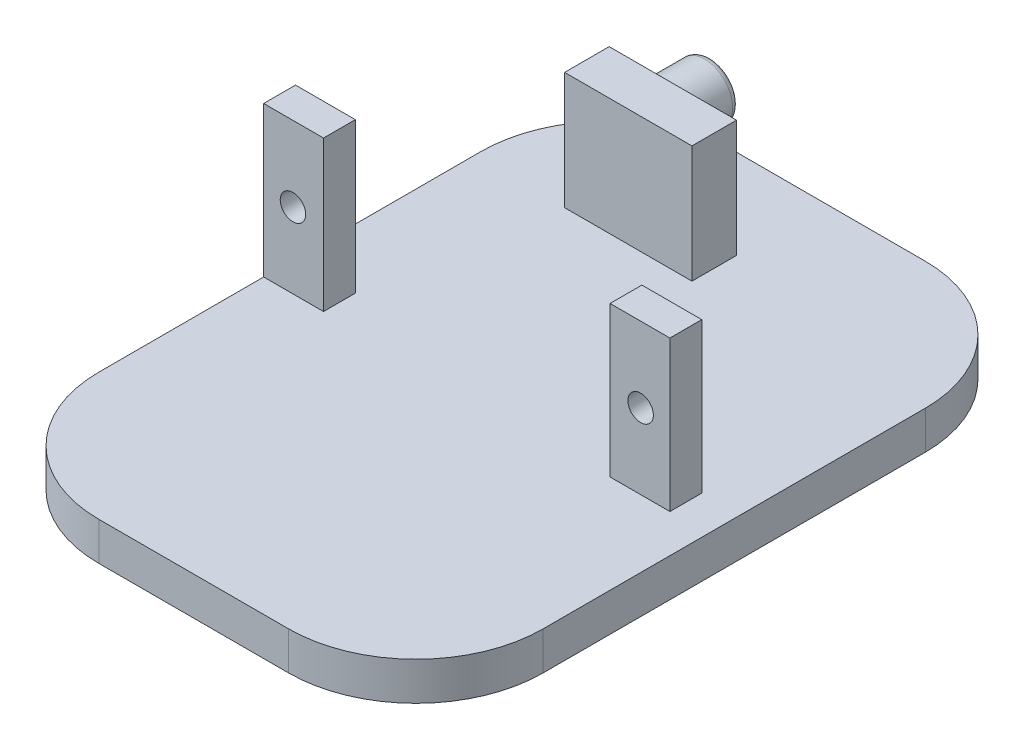
SolidWorks part; units mm, degrees
ref_plane "Plan de face" through (0, 0, 0) normal (0, 0, 1) x (1, 0, 0)
ref_plane "Plan de dessus" through (0, 0, 0) normal (0, 1, 0) x (1, 0, 0)
ref_plane "Plan de droite" through (0, 0, 0) normal (1, 0, 0) x (0, 0, -1)
sketch "Esquisse1" plane through (0, 0, 0) normal (0, 0, 1) x (1, 0, 0)
  line L1 (0, 0) -> (34.9, 0)
  line L2 (0, 0) -> (0, 3)
  line L3 (0, 3) -> (34.9, 3)
  line L4 (34.9, 0) -> (34.9, 3)
  dimension "D1" = 3
  dimension "D2" = 34.9
extrude "Boss.-Extru.1" add sketch "Esquisse1" along normal blind 50
sketch "Esquisse2" plane through (0, 3, 0) normal (0, 1, 0) x (1, 0, 0)
  line L0 (17.45, 0) -> (17.45, -50) construction
  line L1 (34.9, 0) -> (0, 0) construction
  line L2 (34.9, -50) -> (0, -50) construction
  line L3 (31.9, -50) -> (31.9, 0) construction
  line L4 (3, -50) -> (3, 0) construction
  line L5 (31.9, -25) -> (3, -25) construction
  line L7 (17.1, -10.52) -> (7.1, -10.52)
  line L12 (17.1, -10.52) -> (17.1, -7.02)
  line L13 (17.1, -7.02) -> (7.1, -7.02)
  line L14 (7.1, -10.52) -> (7.1, -7.02)
  dimension "D1" = 3
  dimension "D2" = 10.52
  dimension "D3" = 10
  dimension "D4" = 3.5
  dimension "D5" = 0.35
extrude "Boss.-Extru.2" add sketch "Esquisse2" along normal blind 9.2 contours L7 L14 L13 L12
sketch "Esquisse3" plane through (0, 0, 7.02) normal (0, 0, -1) x (-1, 0, 0)
  circle A0 centre (-10.6, 8.9) radius 2.2
  dimension "D1" = 4.4
extrude "Boss.-Extru.3" add sketch "Esquisse3" along normal up to surface (4.5 mm away)
fillet "Congé1" radius 0.5 1 edges at (10.6, 11.1, 2.52)
sketch "Esquisse5" plane through (0, 3, 0) normal (0, 1, 0) x (1, 0, 0)
  line L0 (15.95, -50) -> (15.95, 0) construction
  line L1 (27.2, -27.05) -> (31.9, -27.05)
  line L2 (27.2, -27.05) -> (27.2, -24.55)
  line L3 (27.2, -24.55) -> (31.9, -24.55)
  line L4 (31.9, -27.05) -> (31.9, -24.55)
  line L7 (4.7, -24.55) -> (0, -24.55)
  line L8 (0, -27.05) -> (0, -24.55)
  line L9 (4.7, -27.05) -> (0, -27.05)
  line L10 (4.7, -27.05) -> (4.7, -24.55)
  line L11 (31.9, -27.05) -> (27.2, -27.05) construction
  line L13 (0, -50) -> (0, 0) construction
  point P7 (0, 0)
  point P15 (31.9, -24.55)
  point P16 (32.7206, -24.4053)
  dimension "D1" = 4.7
  dimension "D2" = 2.5
  dimension "D3" = 22.5
extrude "Boss.-Extru.5" add sketch "Esquisse5" along normal up to surface (11.8 mm away) contours L7 L8 L9 L10 | L3 L4 L1 L2
sketch "Esquisse6" plane through (0, 0, 27.05) normal (0, 0, 1) x (1, 0, 0)
  circle A0 centre (29.6, 8.9) radius 1
  circle A1 centre (2.3, 8.9) radius 1
  dimension "D1" = 2
  dimension "D2" = 2
extrude "Enlèv. mat.-Extru.1" cut sketch "Esquisse6" against normal up to next
fillet "Congé2" radius 10 4 edges at (34.9, 1.5, 50) (34.9, 1.5, 0) (0, 1.5, 0) (0, 1.5, 50)
